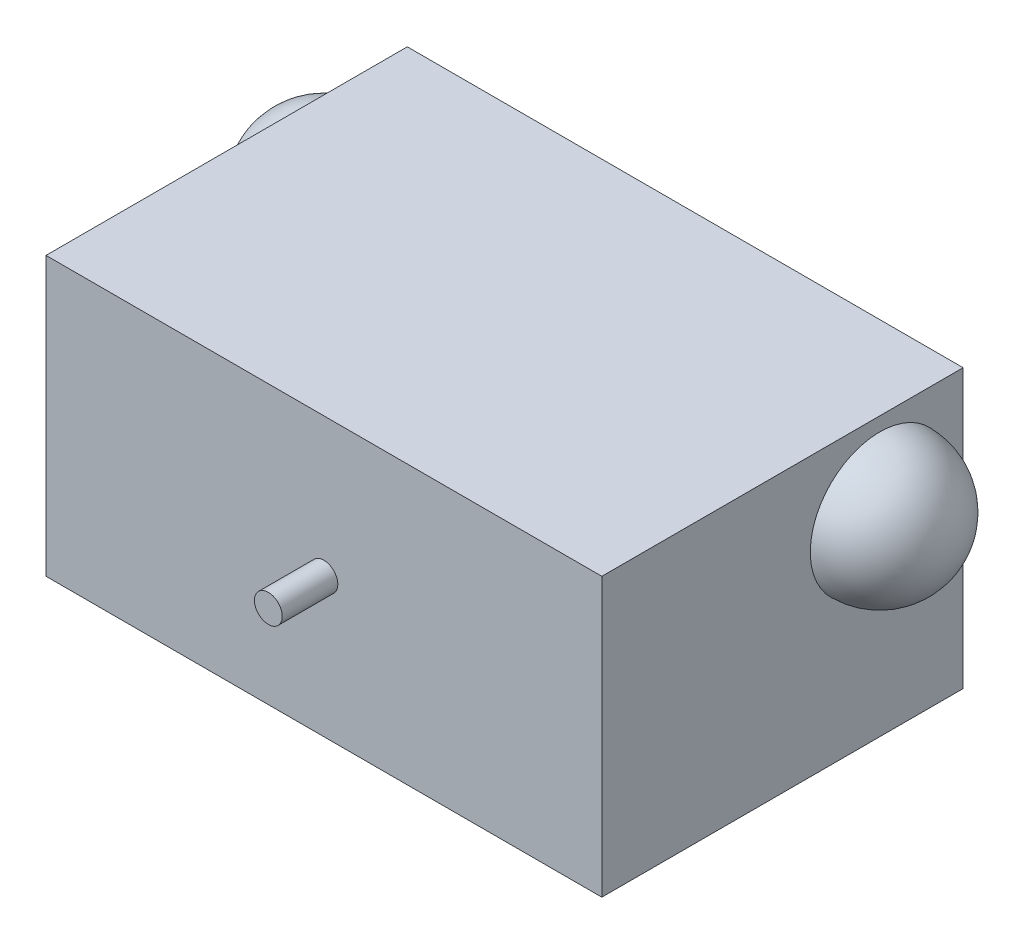
SolidWorks part; units mm, degrees
ref_plane "Front Plane" through (0, 0, 0) normal (0, 0, 1) x (1, 0, 0)
ref_plane "Top Plane" through (0, 0, 0) normal (0, 1, 0) x (1, 0, 0)
ref_plane "Right Plane" through (0, 0, 0) normal (1, 0, 0) x (0, 0, -1)
sketch "Sketch2" plane through (0, 0, 0) normal (0, 1, 0) x (1, 0, 0)
  line L1 (-100, -65) -> (100, -65)
  line L2 (-100, -65) -> (-100, 65)
  line L3 (-100, 65) -> (100, 65)
  line L4 (100, -65) -> (100, 65)
  line L5 (-100, -65) -> (100, 65) construction
  line L6 (-100, 65) -> (100, -65) construction
  point P0 (0, 0)
  dimension "D1" = 130
  dimension "D2" = 200
extrude "Boss-Extrude1" add sketch "Sketch2" along normal blind 50 and the other way blind 50
sketch "Sketch4" plane through (0, 0, 65) normal (0, 0, 1) x (1, 0, 0)
  circle A0 centre (0, 0) radius 5
extrude "Boss-Extrude2" add sketch "Sketch4" along normal blind 20
sketch "Sketch6" plane through (-100, 0, 0) normal (-1, 0, 0) x (0, 0, 1)
  line L3 (-35, -5) -> (-35, 45)
  arc A1 (-35, 45) -> (-35, -5) centre (-35, 20) cw
  dimension "D1" = 50
  dimension "D2" = 25
revolve "Revolve1" add sketch "Sketch6" angle 360 about L3
mirror "Mirror1" about plane through (0, 0, 0) normal (1, 0, 0) of "Revolve1"
